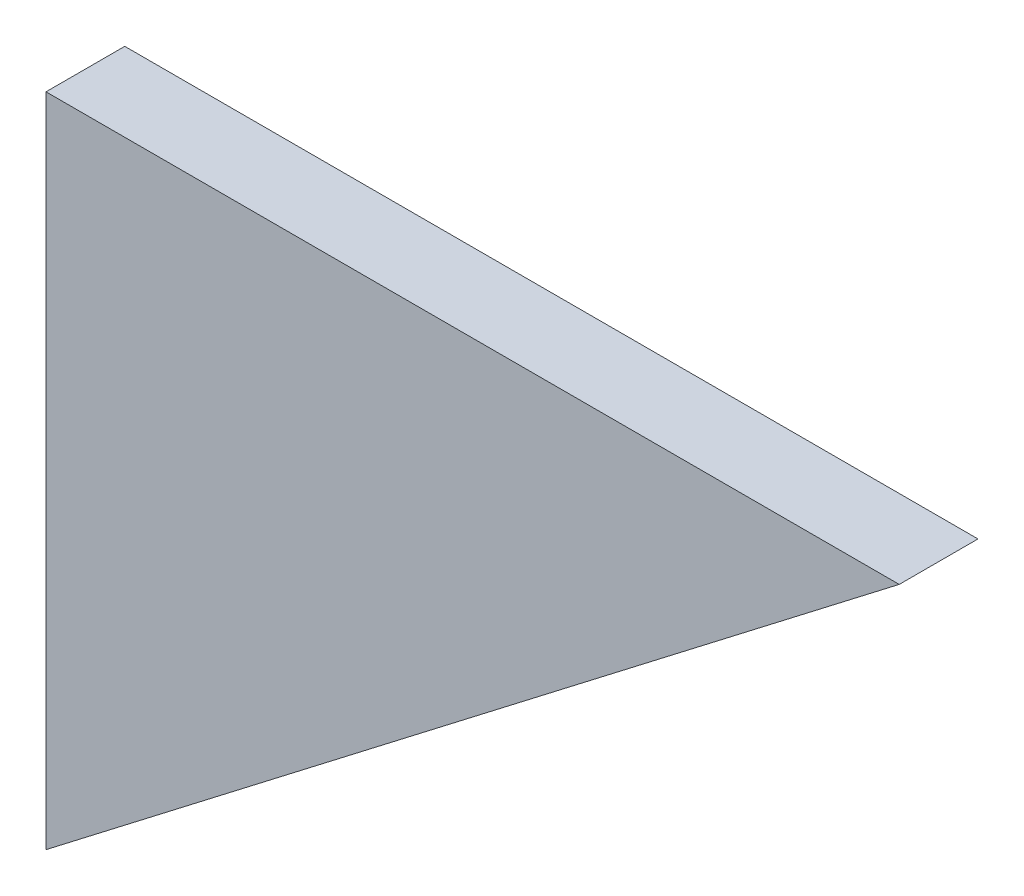
SolidWorks part; units mm, degrees
material "Клен"
ref_plane "Спереди" through (0, 0, 0) normal (0, 0, 1) x (1, 0, 0)
ref_plane "Сверху" through (0, 0, 0) normal (0, 1, 0) x (1, 0, 0)
ref_plane "Справа" through (0, 0, 0) normal (1, 0, 0) x (0, 0, -1)
sketch "Эскиз1" plane through (0, 0, 0) normal (0, 0, 1) x (1, 0, 0)
  line L5 (6, -293.8462) -> (6, -343.8462)
  line L7 (6, -343.8462) -> (71, -293.8462)
  line L9 (71, -293.8462) -> (6, -293.8462)
  point P2 (0, 0)
  dimension "D1" = 50
  dimension "D2" = 65
extrude "Бобышка-Вытянуть1" add sketch "Эскиз1" against normal blind 6 contours L7 L9 L5
